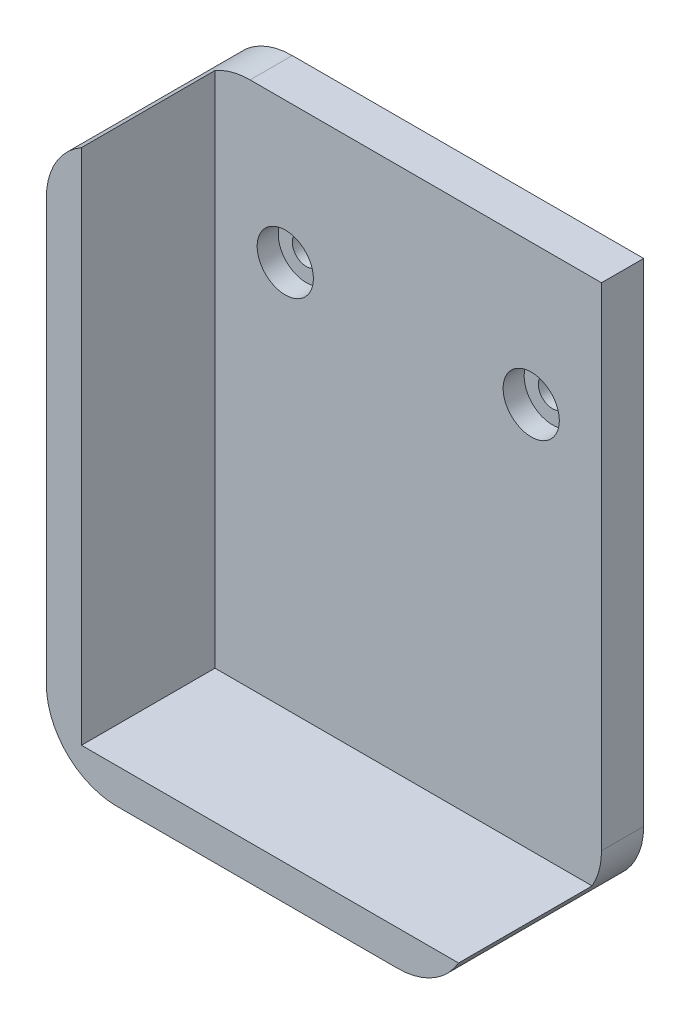
SolidWorks part; units mm, degrees
ref_plane "Front Plane" through (0, 0, 0) normal (0, 0, 1) x (1, 0, 0)
ref_plane "Top Plane" through (0, 0, 0) normal (0, 1, 0) x (1, 0, 0)
ref_plane "Right Plane" through (0, 0, 0) normal (1, 0, 0) x (0, 0, -1)
sketch "Sketch1" plane through (0, 0, 0) normal (0, 0, 1) x (1, 0, 0)
  line L0 (5, 80) -> (5, 5)
  line L1 (0, 0) -> (60, 0)
  line L2 (0, 0) -> (0, 80)
  line L5 (5, 5) -> (76, 5)
  line L7 (0, 80) -> (60, 80)
  line L8 (60, 80) -> (60, 0)
  circle A1 centre (50, 60) radius 2
  circle A2 centre (15, 60) radius 2
  circle A3 centre (15, 60) radius 4
  circle A4 centre (50, 60) radius 4
  dimension "D5" = 10
  dimension "D7" = 10
  dimension "D6" = 20
  dimension "D1" = 60
  dimension "D2" = 80
  dimension "D3" = 5
  dimension "D4" = 5
extrude "Boss-Extrude4" add sketch "Sketch1" along normal blind 6 contours L0 L5 A4 A3 | L5 L0 L2 L1 | A3 A2 | A2 | A4 A1 | A1 region at (32.5, 42.0629, 0) region at (4, 42.5, 0) region at (50, 60, 0) region at (15, 60, 0) region at (11.1131, 60, 0) region at (46.1131, 60, 0)
extrude "Boss-Extrude5" add sketch "Sketch1<12>" along normal blind 25 contours L5 L0 L2 L1 region at (4, 42.5, 0)
sketch "Sketch1<12>" plane through (0, 0, 0) normal (0, 0, 1) x (1, 0, 0) same geometry as "Sketch1"
extrude "Cut-Extrude1" cut sketch "Sketch1<15>" along normal blind 25 contours A2 | A1 region at (50, 60, 0) region at (15, 60, 0)
sketch "Sketch1<15>" plane through (0, 0, 0) normal (0, 0, 1) x (1, 0, 0) same geometry as "Sketch1"
extrude "Cut-Extrude2" cut sketch "Sketch1<16>" along normal blind 25 contours A4 A1 | A3 A2 region at (11.1131, 60, 0) region at (46.1131, 60, 0)
sketch "Sketch1<16>" plane through (0, 0, 0) normal (0, 0, 1) x (1, 0, 0) same geometry as "Sketch1"
extrude "Boss-Extrude7" add sketch "Sketch1<18>" along normal blind 3 contours A4 A1 | A3 A2 region at (11.1131, 60, 0) region at (46.1131, 60, 0)
sketch "Sketch1<18>" plane through (0, 0, 0) normal (0, 0, 1) x (1, 0, 0) same geometry as "Sketch1"
fillet "Fillet1" radius 10 3 edges at (60, 0, 12.5) (0, 80, 12.5) (0, 0, 12.5)
